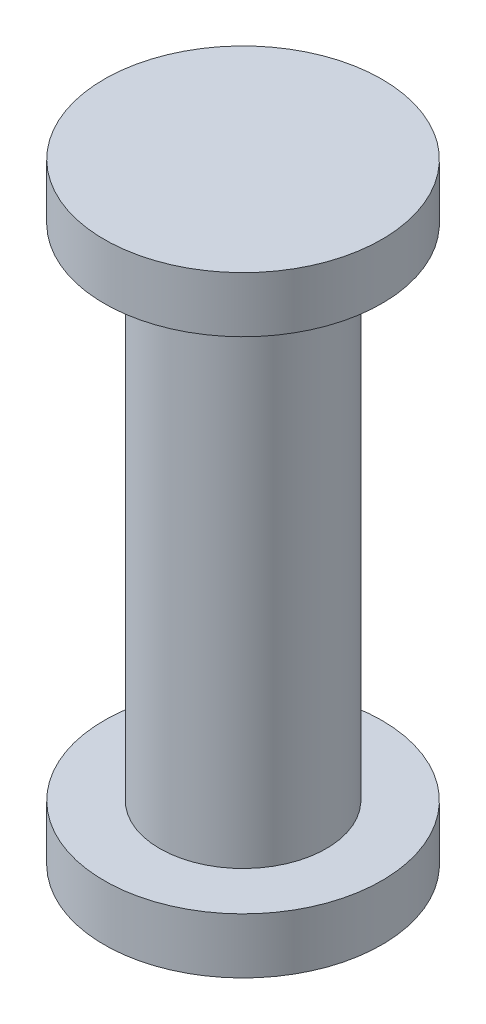
SolidWorks part; units mm, degrees
material "1023 Листовая углеродистая сталь (SS)"
ref_plane "Спереди" through (0, 0, 0) normal (0, 0, 1) x (1, 0, 0)
ref_plane "Сверху" through (0, 0, 0) normal (0, 1, 0) x (1, 0, 0)
ref_plane "Справа" through (0, 0, 0) normal (1, 0, 0) x (0, 0, -1)
sketch "Эскиз1" plane through (0, 0, 0) normal (0, 0, 1) x (1, 0, 0)
  line L0 (0, 0) -> (0, 11)
  line L1 (0, 11) -> (-2.5, 11)
  line L3 (-1.5, 10) -> (-1.5, 1)
  line L4 (-1.5, 1) -> (-2.5, 1)
  line L5 (-2.5, 1) -> (-2.5, 0)
  line L6 (-2.5, 0) -> (0, 0)
  line L7 (-2.5, 11) -> (-2.5, 10)
  line L8 (-2.5, 10) -> (-1.5, 10)
  dimension "D1" = 11
  dimension "D2" = 1
  dimension "D3" = 2.5
  dimension "D4" = 1.5
revolve "Повернуть1" add sketch "Эскиз1" angle 360 about L0
